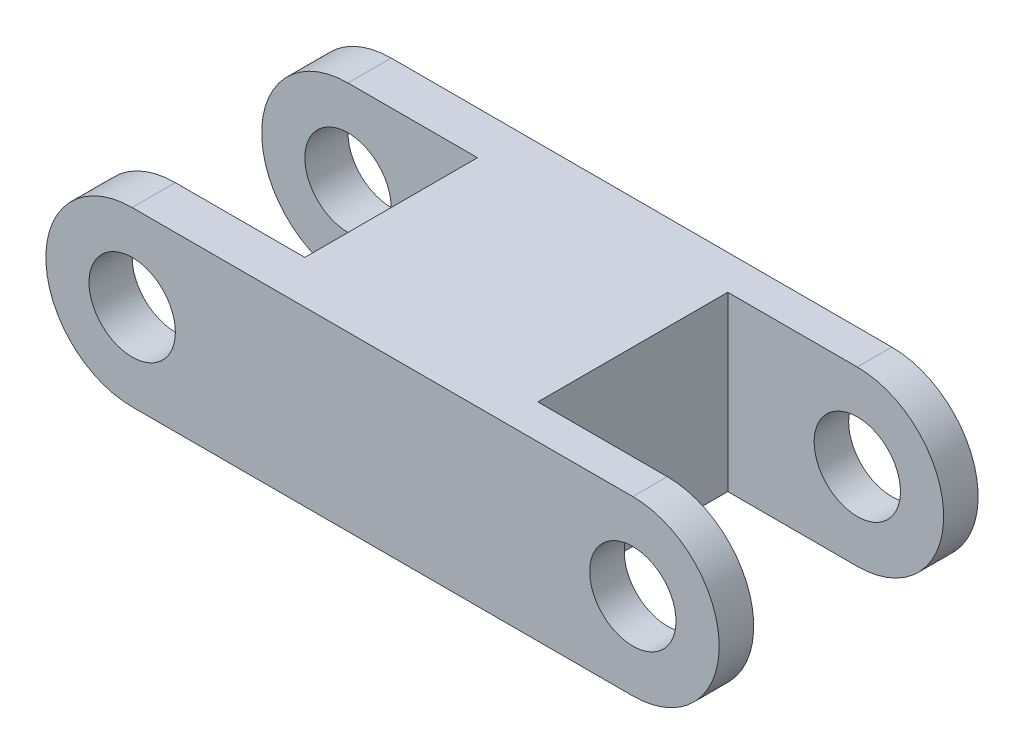
SolidWorks part; units mm, degrees
ref_plane "Front Plane" through (0, 0, 0) normal (0, 0, 1) x (1, 0, 0)
ref_plane "Top Plane" through (0, 0, 0) normal (0, 1, 0) x (1, 0, 0)
ref_plane "Right Plane" through (0, 0, 0) normal (1, 0, 0) x (0, 0, -1)
sketch "Sketch1" plane through (0, 0, 0) normal (0, 0, 1) x (1, 0, 0)
  line L0 (0, 0) -> (57.9939, 0) construction
  line L1 (0, 10) -> (57.9939, 10)
  line L2 (0, -10) -> (57.9939, -10)
  arc A0 (0, 10) -> (0, -10) centre (0, 0) ccw
  arc A1 (57.9939, -10) -> (57.9939, 10) centre (57.9939, 0) ccw
  circle A2 centre (0, 0) radius 5
  circle A3 centre (57.9939, 0) radius 5
  point P3 (28.9969, 0)
  dimension "D1" = 10
  dimension "D2" = 10
  dimension "D3" = 20
extrude "Boss-Extrude1" add sketch "Sketch1" along normal blind 30
sketch "Sketch2" plane through (0, 10, 0) normal (0, 1, 0) x (1, 0, 0)
  line L0 (-10, 0) -> (-10, -30) construction
  line L1 (15, -5) -> (-10, -5)
  line L2 (15, -5) -> (15, -25)
  line L3 (15, -25) -> (-10, -25)
  line L4 (-10, -5) -> (-10, -25)
  line L5 (67.9939, -30) -> (67.9939, 0) construction
  line L6 (0, -30) -> (0, 0) construction
  line L15 (42.9939, -26) -> (67.9939, -26)
  line L16 (42.9939, -26) -> (42.9939, -4)
  line L17 (42.9939, -4) -> (67.9939, -4)
  line L18 (67.9939, -26) -> (67.9939, -4)
  line L19 (57.9939, -30) -> (57.9939, 0) construction
  point P7 (-10, -15)
  point P10 (0, -15)
  point P15 (67.9939, -15)
  point P19 (57.9939, -15)
  dimension "D1" = 20
  dimension "D2" = 25
  dimension "D3" = 22
  dimension "D4" = 25
extrude "Cut-Extrude1" cut sketch "Sketch2" against normal through all
